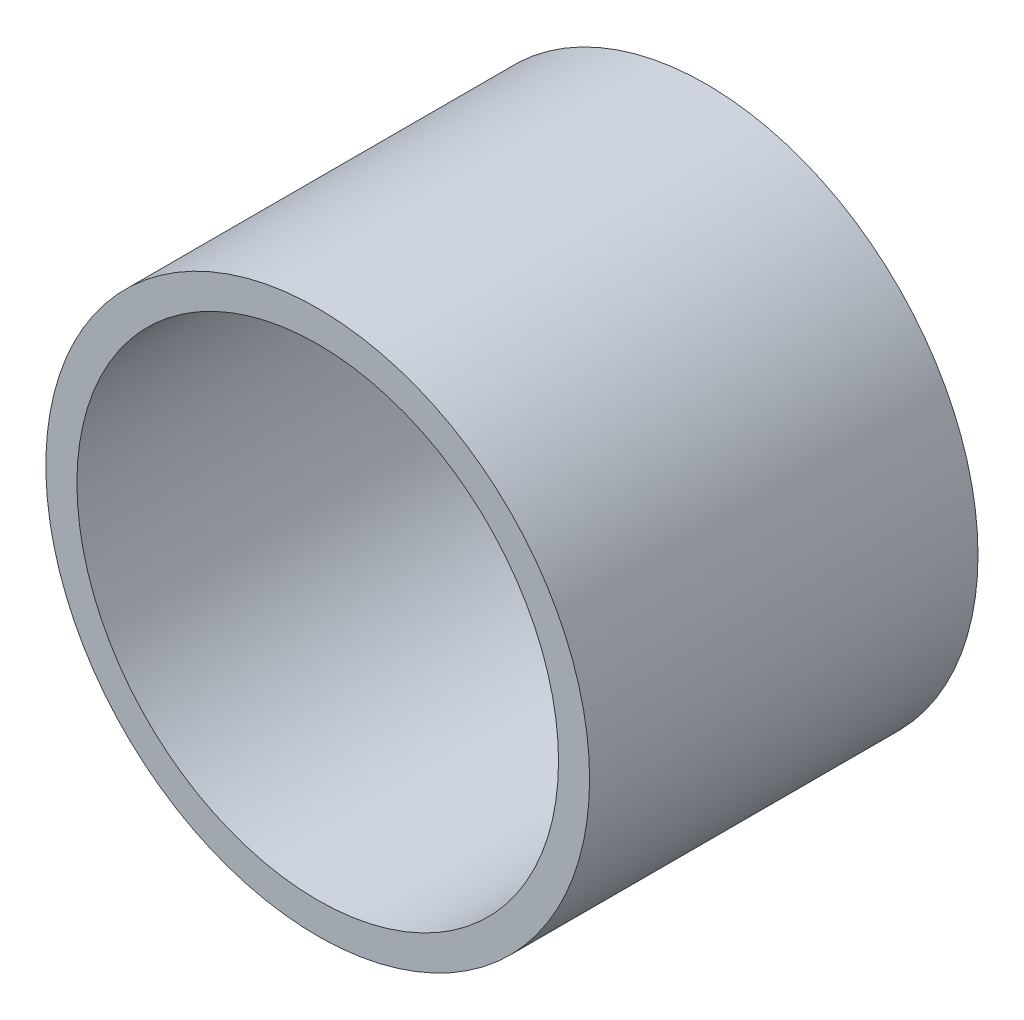
SolidWorks part; units mm, degrees
ref_plane "Спереди" through (0, 0, 0) normal (0, 0, 1) x (1, 0, 0)
ref_plane "Сверху" through (0, 0, 0) normal (0, 1, 0) x (1, 0, 0)
ref_plane "Справа" through (0, 0, 0) normal (1, 0, 0) x (0, 0, -1)
sketch "Эскиз1" plane through (0, 0, 0) normal (0, 0, 1) x (1, 0, 0)
  circle A0 centre (0, 0) radius 3.5
  circle A1 centre (0, 0) radius 3.1
extrude "Бобышка-Вытянуть1" add sketch "Эскиз1" along normal blind 5
